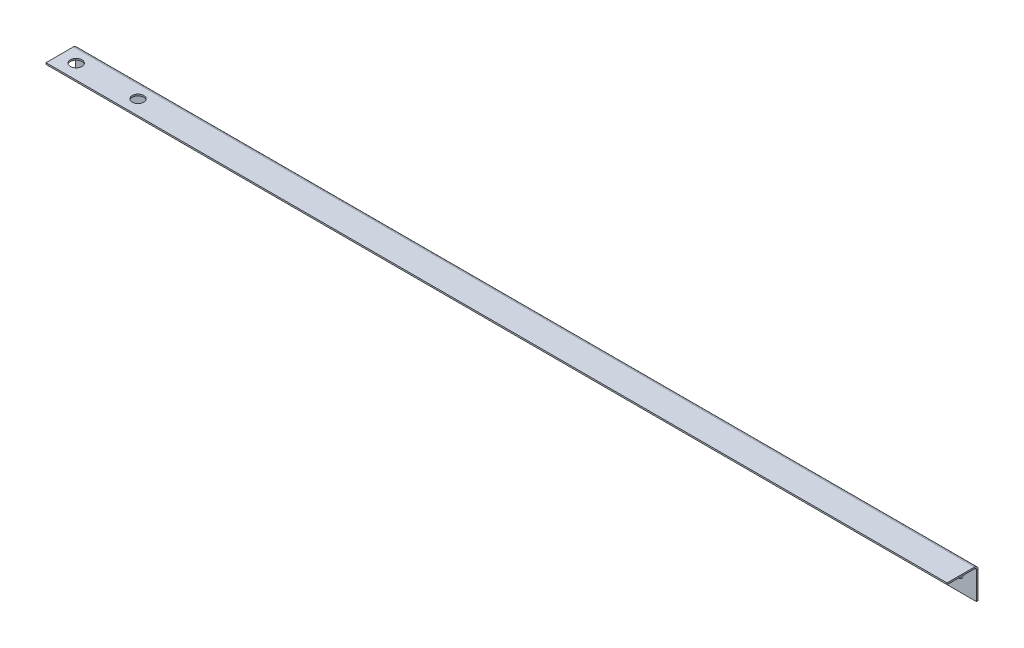
SolidWorks part; units mm, degrees
note: The reader was unsure of these and kept them because the rebuilt part matched: flange length of "Edge-Flange1".
material "ASTM A36 Steel"
ref_plane "Front Plane" through (0, 0, 0) normal (0, 0, 1) x (1, 0, 0)
ref_plane "Top Plane" through (0, 0, 0) normal (0, 1, 0) x (1, 0, 0)
ref_plane "Right Plane" through (0, 0, 0) normal (1, 0, 0) x (0, 0, -1)
sketch "Sketch1" plane through (0, 0, 0) normal (0, 0, 1) x (1, 0, 0)
  line L0 (474.5557, 62.8577) -> (459.5557, 62.8577) construction
  line L1 (497.0557, 82.8577) -> (-667.9443, 82.8577)
  line L2 (497.0557, 82.8577) -> (497.0557, 42.8577)
  line L3 (497.0557, 42.8577) -> (-667.9443, 42.8577)
  line L4 (-667.9443, 82.8577) -> (-667.9443, 42.8577)
  line L5 (474.5557, 57.8577) -> (459.5557, 57.8577)
  line L6 (474.5557, 67.8577) -> (459.5557, 67.8577)
  line L7 (374.5557, 62.8577) -> (359.5557, 62.8577) construction
  line L8 (374.5557, 57.8577) -> (359.5557, 57.8577)
  line L9 (374.5557, 67.8577) -> (359.5557, 67.8577)
  arc A0 (474.5557, 57.8577) -> (474.5557, 67.8577) centre (474.5557, 62.8577) ccw
  arc A1 (459.5557, 67.8577) -> (459.5557, 57.8577) centre (459.5557, 62.8577) ccw
  arc A2 (374.5557, 57.8577) -> (374.5557, 67.8577) centre (374.5557, 62.8577) ccw
  arc A3 (359.5557, 67.8577) -> (359.5557, 57.8577) centre (359.5557, 62.8577) ccw
  point P6 (467.0557, 62.8577)
  point P11 (367.0557, 62.8577)
  dimension "D3" = 15
  dimension "D1" = 1165
  dimension "D2" = 40
  dimension "D4" = 30
  dimension "D5" = 10
  dimension "D6" = 15
  dimension "D7" = 100
  dimension "D8" = 20
base flange "Base-Flange1" sketch "Sketch1" thickness 2 reverse thickness direction no parameters "D1"=2.5
edge flange "Edge-Flange1" sketch "Sketch8" flange angle 90 flange length 40 flange position material inside bend radius 2.5 thickness 2 relief rectangular parameters "D6"=10
sketch "Sketch8" plane through (0, 82.8577, 0) normal (0, -1, 0) x (1, 0, 0)
  line L1 (497.0557, 0) -> (-667.9443, 0) construction
  line L2 (-667.9443, 0) -> (-667.9443, 38)
  line L3 (-667.9443, 38) -> (497.0557, 38)
  line L4 (497.0557, 38) -> (497.0557, 0)
  line L5 (497.0557, 0) -> (-667.9443, 0)
bend "EdgeBend1" bend radius 2.5 bend angle 90 parameters "D5"=1
sketch "Sketch9" plane through (0, 80.8577, 0) normal (0, -1, 0) x (1, 0, 0)
  line L0 (-667.9443, 38) -> (-667.9443, 2.5) construction
  circle A0 centre (-647.9443, 19) radius 7.5
  circle A1 centre (-567.9443, 19) radius 7.5
  dimension "D1" = 20
  dimension "D2" = 80
  dimension "D3" = 15
  dimension "D4" = 15
extrude "Cut-Extrude1" cut sketch "Sketch9" against normal through all normal cut yes
sketch "Bend-Lines1" [suppressed] plane through (0, 0, 0) normal (0, 1, 0) x (1, 0, 0)
sketch "Bounding-Box1" [suppressed] plane through (0, 0, 0) normal (0, 1, 0) x (1, 0, 0)
sheet metal parameters "Sheet-Metal1" thickness 2 parameters "D1"=2.5
flat pattern "Flat-Pattern1" [suppressed]
sketch "Bend-Lines2" plane through (0, 0, 0) normal (0, 1, 0) x (1, 0, 0)
sketch3d "Bounding-Box2" [suppressed]
  line L0 (667.9443, 42.8577, 0) -> (-497.0557, 42.8577, 0) construction
  line L1 (667.9443, 82.8577, 0) -> (-497.0557, 82.8577, 0) construction
  line L2 (667.9443, 42.8577, 0) -> (667.9443, 82.8577, 0) construction
  line L3 (-497.0557, 42.8577, 0) -> (-497.0557, 82.8577, 0) construction
sheet metal parameters "Sheet-Metal2" thickness 2 parameters "D1"=2.5
flat pattern "Flat-Pattern1"
sketch "Bend-Lines2" plane through (0, 0, 0) normal (0, 0, 1) x (1, 0, 0)
  line L0 (497.0557, 81.1066) -> (-667.9443, 81.1066) construction
  line L1 (497.0557, 81.1066) -> (-667.9443, 81.1066) construction
sketch3d "Bounding-Box2" [suppressed]
  line L0 (-667.9443, 42.8577, 0) -> (497.0557, 42.8577, 0) construction
  line L1 (-667.9443, 119.3555, 0) -> (497.0557, 119.3555, 0) construction
  line L2 (-667.9443, 42.8577, 0) -> (-667.9443, 119.3555, 0) construction
  line L3 (497.0557, 42.8577, 0) -> (497.0557, 119.3555, 0) construction
bend of the flat pattern "Flatten-<EdgeBend1>1"
sheet metal parameters "Sheet-Metal3" thickness 2 parameters "D1"=2.5
flat pattern "Flat-Pattern1"
sketch "Bend-Lines2" plane through (0, 0, 0) normal (0, 0, 1) x (1, 0, 0)
  line L0 (497.0557, 81.1066) -> (-667.9443, 81.1066) construction
  line L1 (497.0557, 81.1066) -> (-667.9443, 81.1066) construction
sketch3d "Bounding-Box2" [suppressed]
  line L0 (-667.9443, 42.8577, 0) -> (497.0557, 42.8577, 0) construction
  line L1 (-667.9443, 119.3555, 0) -> (497.0557, 119.3555, 0) construction
  line L2 (-667.9443, 42.8577, 0) -> (-667.9443, 119.3555, 0) construction
  line L3 (497.0557, 42.8577, 0) -> (497.0557, 119.3555, 0) construction
bend of the flat pattern "Flatten-<EdgeBend1>1"
